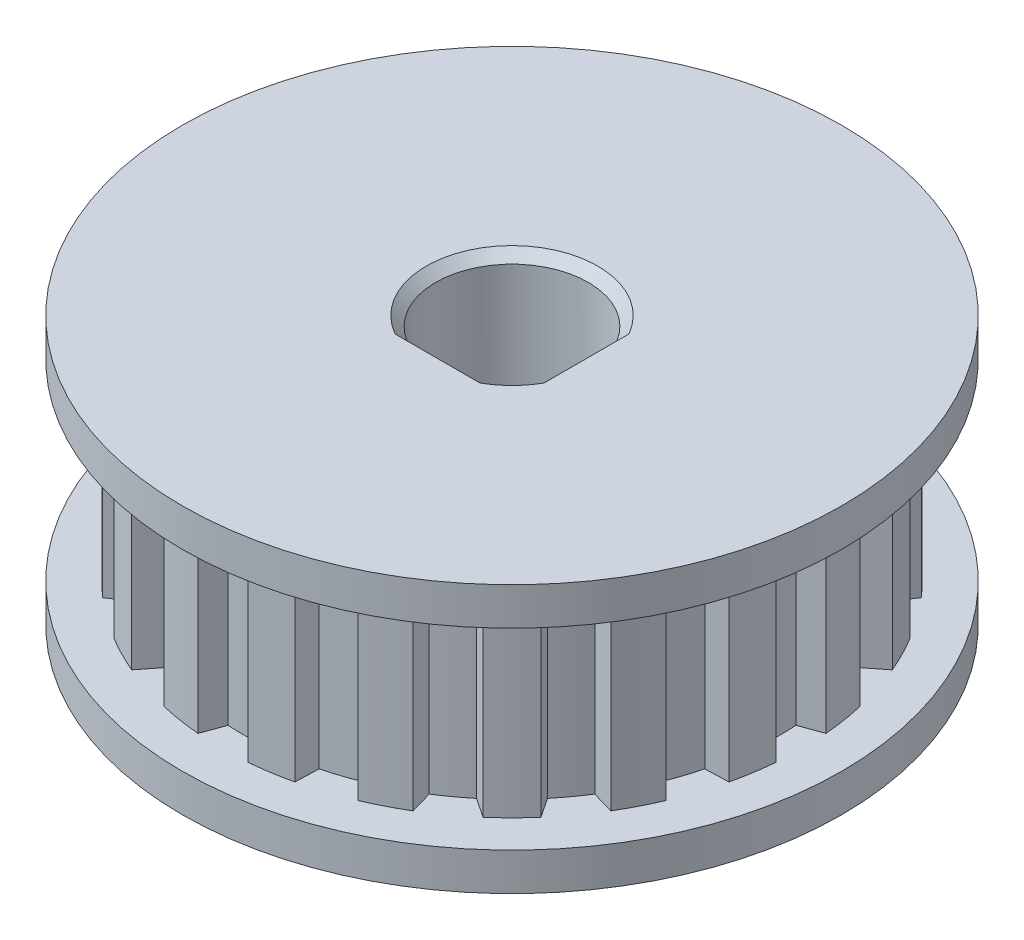
SolidWorks part; units mm, degrees
ref_plane "Спереди" through (0, 0, 0) normal (0, 0, 1) x (1, 0, 0)
ref_plane "Сверху" through (0, 0, 0) normal (0, 1, 0) x (1, 0, 0)
ref_plane "Справа" through (0, 0, 0) normal (1, 0, 0) x (0, 0, -1)
sketch "Эскиз2" plane through (0, 0, 0) normal (0, 1, 0) x (1, 0, 0)
  line L0 (0, 0) -> (0, 16.4) construction
  line L1 (0, 0) -> (2.5655, 16.1981) construction
  line L2 (0, 0) -> (-2.5655, 16.1981) construction
  line L3 (-0.9, 14.1715) -> (-1.3263, 15.3428)
  line L4 (0.9, 14.1715) -> (1.3263, 15.3428)
  line L5 (3.5233, 13.756) -> (3.4798, 15.0017)
  line L6 (5.2352, 13.1997) -> (6.0026, 14.182)
  line L7 (7.6017, 11.994) -> (7.9452, 13.1922)
  line L8 (9.0579, 10.9359) -> (10.0913, 11.633)
  line L9 (10.9359, 9.0579) -> (11.633, 10.0913)
  line L10 (11.994, 7.6017) -> (13.1922, 7.9452)
  line L11 (13.1997, 5.2352) -> (14.182, 6.0026)
  line L12 (13.756, 3.5233) -> (15.0017, 3.4798)
  line L13 (14.1715, 0.9) -> (15.3428, 1.3263)
  line L14 (14.1715, -0.9) -> (15.3428, -1.3263)
  line L15 (13.756, -3.5233) -> (15.0017, -3.4798)
  line L16 (13.1997, -5.2352) -> (14.182, -6.0026)
  line L17 (11.994, -7.6017) -> (13.1922, -7.9452)
  line L18 (10.9359, -9.0579) -> (11.633, -10.0913)
  line L19 (9.0579, -10.9359) -> (10.0913, -11.633)
  line L20 (7.6017, -11.994) -> (7.9452, -13.1922)
  line L21 (5.2352, -13.1997) -> (6.0026, -14.182)
  line L22 (3.5233, -13.756) -> (3.4798, -15.0017)
  line L23 (0.9, -14.1715) -> (1.3263, -15.3428)
  line L24 (-0.9, -14.1715) -> (-1.3263, -15.3428)
  line L25 (-3.5233, -13.756) -> (-3.4798, -15.0017)
  line L26 (-5.2352, -13.1997) -> (-6.0026, -14.182)
  line L27 (-7.6017, -11.994) -> (-7.9452, -13.1922)
  line L28 (-9.0579, -10.9359) -> (-10.0913, -11.633)
  line L29 (-10.9359, -9.0579) -> (-11.633, -10.0913)
  line L30 (-11.994, -7.6017) -> (-13.1922, -7.9452)
  line L31 (-13.1997, -5.2352) -> (-14.182, -6.0026)
  line L32 (-13.756, -3.5233) -> (-15.0017, -3.4798)
  line L33 (-14.1715, -0.9) -> (-15.3428, -1.3263)
  line L34 (-14.1715, 0.9) -> (-15.3428, 1.3263)
  line L35 (-13.756, 3.5233) -> (-15.0017, 3.4798)
  line L36 (-13.1997, 5.2352) -> (-14.182, 6.0026)
  line L37 (-11.994, 7.6017) -> (-13.1922, 7.9452)
  line L38 (-10.9359, 9.0579) -> (-11.633, 10.0913)
  line L39 (-9.0579, 10.9359) -> (-10.0913, 11.633)
  line L40 (-7.6017, 11.994) -> (-7.9452, 13.1922)
  line L41 (-5.2352, 13.1997) -> (-6.0026, 14.182)
  line L42 (-3.5233, 13.756) -> (-3.4798, 15.0017)
  circle A0 centre (0, 0) radius 16.4 construction
  circle A1 centre (0, 0) radius 15.9 construction
  circle A2 centre (0, 0) radius 15.4 construction
  circle A3 centre (0, 0) radius 14.2 construction
  arc A4 (-0.9, 14.1715) -> (0.9, 14.1715) centre (0, 0) cw
  arc A5 (3.5233, 13.756) -> (5.2352, 13.1997) centre (0, 0) cw
  arc A6 (7.6017, 11.994) -> (9.0579, 10.9359) centre (0, 0) cw
  arc A7 (10.9359, 9.0579) -> (11.994, 7.6017) centre (0, 0) cw
  arc A8 (13.1997, 5.2352) -> (13.756, 3.5233) centre (0, 0) cw
  arc A9 (14.1715, 0.9) -> (14.1715, -0.9) centre (0, 0) cw
  arc A10 (13.756, -3.5233) -> (13.1997, -5.2352) centre (0, 0) cw
  arc A11 (11.994, -7.6017) -> (10.9359, -9.0579) centre (0, 0) cw
  arc A12 (9.0579, -10.9359) -> (7.6017, -11.994) centre (0, 0) cw
  arc A13 (5.2352, -13.1997) -> (3.5233, -13.756) centre (0, 0) cw
  arc A14 (0.9, -14.1715) -> (-0.9, -14.1715) centre (0, 0) cw
  arc A15 (-3.5233, -13.756) -> (-5.2352, -13.1997) centre (0, 0) cw
  arc A16 (-7.6017, -11.994) -> (-9.0579, -10.9359) centre (0, 0) cw
  arc A17 (-10.9359, -9.0579) -> (-11.994, -7.6017) centre (0, 0) cw
  arc A18 (-13.1997, -5.2352) -> (-13.756, -3.5233) centre (0, 0) cw
  arc A19 (-14.1715, -0.9) -> (-14.1715, 0.9) centre (0, 0) cw
  arc A20 (-13.756, 3.5233) -> (-13.1997, 5.2352) centre (0, 0) cw
  arc A21 (-11.994, 7.6017) -> (-10.9359, 9.0579) centre (0, 0) cw
  arc A22 (-9.0579, 10.9359) -> (-7.6017, 11.994) centre (0, 0) cw
  arc A23 (-5.2352, 13.1997) -> (-3.5233, 13.756) centre (0, 0) cw
  arc A24 (-3.4798, 15.0017) -> (-1.3263, 15.3428) centre (0, 0) cw
  arc A25 (1.3263, 15.3428) -> (3.4798, 15.0017) centre (0, 0) cw
  arc A26 (6.0026, 14.182) -> (7.9452, 13.1922) centre (0, 0) cw
  arc A27 (10.0913, 11.633) -> (11.633, 10.0913) centre (0, 0) cw
  arc A28 (13.1922, 7.9452) -> (14.182, 6.0026) centre (0, 0) cw
  arc A29 (15.0017, 3.4798) -> (15.3428, 1.3263) centre (0, 0) cw
  arc A30 (15.3428, -1.3263) -> (15.0017, -3.4798) centre (0, 0) cw
  arc A31 (14.182, -6.0026) -> (13.1922, -7.9452) centre (0, 0) cw
  arc A32 (11.633, -10.0913) -> (10.0913, -11.633) centre (0, 0) cw
  arc A33 (7.9452, -13.1922) -> (6.0026, -14.182) centre (0, 0) cw
  arc A34 (3.4798, -15.0017) -> (1.3263, -15.3428) centre (0, 0) cw
  arc A35 (-1.3263, -15.3428) -> (-3.4798, -15.0017) centre (0, 0) cw
  arc A36 (-6.0026, -14.182) -> (-7.9452, -13.1922) centre (0, 0) cw
  arc A37 (-10.0913, -11.633) -> (-11.633, -10.0913) centre (0, 0) cw
  arc A38 (-13.1922, -7.9452) -> (-14.182, -6.0026) centre (0, 0) cw
  arc A39 (-15.0017, -3.4798) -> (-15.3428, -1.3263) centre (0, 0) cw
  arc A40 (-15.3428, 1.3263) -> (-15.0017, 3.4798) centre (0, 0) cw
  arc A41 (-14.182, 6.0026) -> (-13.1922, 7.9452) centre (0, 0) cw
  arc A42 (-11.633, 10.0913) -> (-10.0913, 11.633) centre (0, 0) cw
  arc A43 (-7.9452, 13.1922) -> (-6.0026, 14.182) centre (0, 0) cw
  point P11 (0, 14.2)
  dimension "D1" = 32.8
  dimension "D2" = 31.8
  dimension "D3" = 30.8
  dimension "D4" = 28.4
  dimension "D7" = 1.8
  dimension "D5" = 9
  dimension "D6" = 9
  dimension "D8" = 20
  dimension "D9" = 20
extrude "Вытянуть1" add sketch "Эскиз2" along normal blind 10.2
sketch "Эскиз3" plane through (0, 10.2, 0) normal (0, 1, 0) x (1, 0, 0)
  circle A0 centre (0, 0) radius 17.5
  dimension "D1" = 35
extrude "Вытянуть2" add sketch "Эскиз3" along normal blind 2
sketch "Эскиз4" plane through (0, 0, 0) normal (0, -1, 0) x (1, 0, 0)
  circle A0 centre (0, 0) radius 17.5
  circle A1 centre (0, 0) radius 17.5 construction
extrude "Вытянуть3" add sketch "Эскиз4" along normal blind 2
sketch "Эскиз5" plane through (0, 12.2, 0) normal (0, 1, 0) x (1, 0, 0)
  line L0 (3.45, -2.1213) -> (3.45, 2.1213)
  line L1 (2.1213, -3.45) -> (-2.1213, -3.45)
  circle A0 centre (0, 0) radius 4.05 construction
  arc A1 (2.1213, -3.45) -> (3.45, -2.1213) centre (0, 0) ccw
  arc A2 (-2.1213, -3.45) -> (3.45, 2.1213) centre (0, 0) cw
  dimension "D1" = 8.1
  dimension "D2" = 3.45
  dimension "D3" = 3.45
extrude "Вытянуть4" cut sketch "Эскиз5" against normal blind 10
sketch "Эскиз6" plane through (0, -2, 0) normal (0, -1, 0) x (1, 0, 0)
  circle A0 centre (0, 0) radius 4.05
  dimension "D1" = 8.1
extrude "Вытянуть5" cut sketch "Эскиз6" against normal up to surface (4.2 mm away) up to face at (0.8625, 2.2, 0.8625)
chamfer "Фаска1" distance 0.5 angle 45 4 edges at (3.45, 12.2, 0) (2.8638, 12.2, 2.8638) (0, 12.2, 3.45) (-2.8638, 12.2, -2.8638)
chamfer "Фаска2" distance 0.5 angle 45 1 edges at (0, -2, -4.05)
